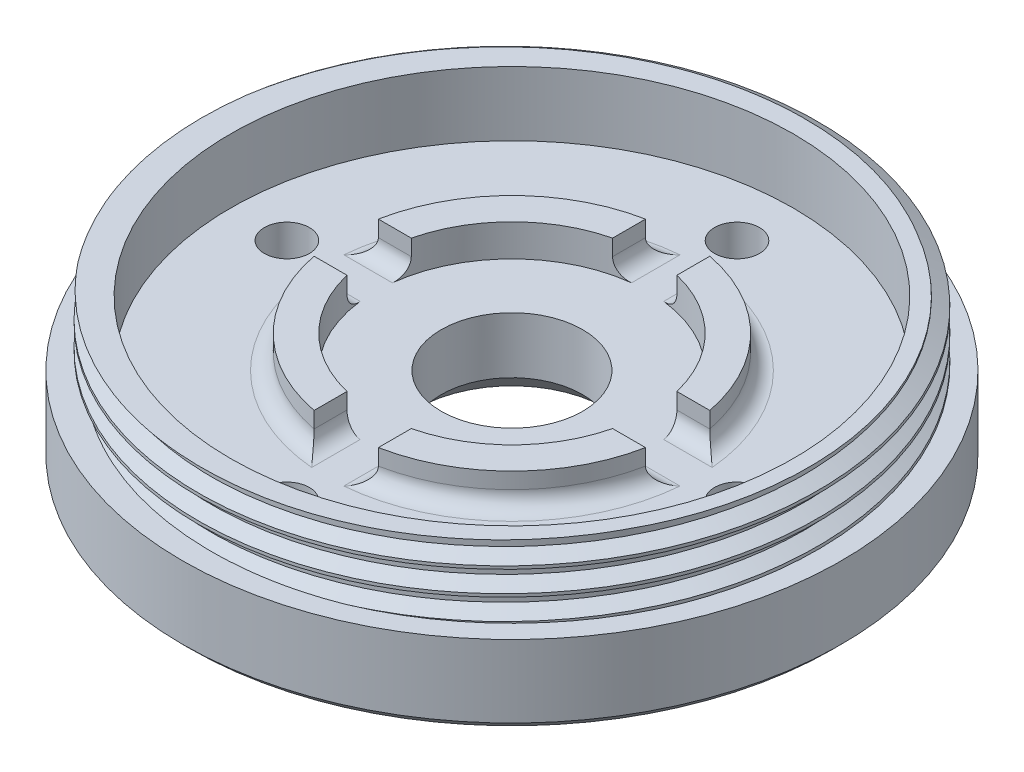
SolidWorks part; units mm, degrees
ref_plane "Front plane" through (0, 0, 0) normal (0, 0, 1) x (1, 0, 0)
ref_plane "Top plane" through (0, 0, 0) normal (0, 1, 0) x (1, 0, 0)
ref_plane "Right plane" through (0, 0, 0) normal (1, 0, 0) x (0, 0, -1)
ref_axis "Axis X" through (0, 0, 0) along (1, 0, 0)
ref_axis "Axis Y" through (0, 0, 0) along (0, 1, 0)
ref_axis "Axis Z" through (0, 0, 0) along (0, 0, 1)
sketch "Sketch1" plane through (0, 0, 0) normal (0, 1, 0) x (1, 0, 0)
  circle A0 centre (0, 0) radius 20.5
  circle A1 centre (0, 0) radius 4.4
  circle A2 centre (0, 0) radius 14 construction
  circle A3 centre (0, 14) radius 1.4
  circle A4 centre (14, 0) radius 1.4
  circle A5 centre (0, -14) radius 1.4
  circle A6 centre (-14, 0) radius 1.4
  point P16 (0, 0)
  dimension "D1" = 41
  dimension "D2" = 8.8
  dimension "D3" = 28
  dimension "D4" = 2.8
  dimension "D5" = 4
extrude "Extrude1" add sketch "Sketch1" along normal blind 5
sketch "Sketch8" plane through (0, 5, 0) normal (0, 1, 0) x (1, 0, 0)
  circle A1 centre (0, 0) radius 17.5
  circle A3 centre (0, 0) radius 18.45
  dimension "D1" = 35
  dimension "D2" = 0.95
extrude "Бобышка-Вытянуть1" add sketch "Sketch8" along normal blind 4
thread "Резьба1" pitch 1.5 method extrude trim with start face yes trim with end face yes profile "Профиль резьбы1" start angle 0, offset 2, length 0, pitch 1.5, diameter 36.9
ref_plane "Плоскость1" through (-18.45, 11, 0) normal (0, 0, 1) x (-1, 0, 0)
sketch "Профиль резьбы1" plane through (-18.45, 11, 0) normal (0, 0, 1) x (-1, 0, 0)
  line L0 (0, 0) -> (0, 1.5) construction
  line L1 (0, 0) -> (0.8119, 0.4687)
  line L2 (0.8119, 0.4687) -> (0.8119, 0.6562)
  line L3 (0.8119, 0.6562) -> (0, 1.125)
  line L4 (0.8119, 0.5625) -> (0, 0.5625) construction
  line L11 (0, 0) -> (0, 1.125)
  point P2 (0, 0)
  dimension "Pitch" = 1.5
  dimension "Profile_Angle" = 60
  dimension "Profile_Land" = 0.1875
  dimension "Profile_Height" = 0.8119
sketch "Эскиз3" plane through (0, 5, 0) normal (0, 1, 0) x (1, 0, 0)
  line L0 (0, 0) -> (0, 10) construction
  line L1 (-2, 10.3078) -> (-2, 8.2614)
  line L2 (2, 10.3078) -> (2, 8.2614)
  line L3 (10.3078, 2) -> (8.2614, 2)
  line L4 (10.3078, -2) -> (8.2614, -2)
  line L5 (2, -10.3078) -> (2, -8.2614)
  line L6 (-2, -10.3078) -> (-2, -8.2614)
  line L7 (-10.3078, -2) -> (-8.2614, -2)
  line L8 (-10.3078, 2) -> (-8.2614, 2)
  arc A0 (-2, 8.2614) -> (-8.2614, 2) centre (0, 0) ccw
  arc A1 (-2, 10.3078) -> (-10.3078, 2) centre (0, 0) ccw
  arc A2 (8.2614, 2) -> (2, 8.2614) centre (0, 0) ccw
  arc A3 (10.3078, 2) -> (2, 10.3078) centre (0, 0) ccw
  arc A4 (-8.2614, -2) -> (-2, -8.2614) centre (0, 0) ccw
  arc A5 (-10.3078, -2) -> (-2, -10.3078) centre (0, 0) ccw
  arc A6 (2, -8.2614) -> (8.2614, -2) centre (0, 0) ccw
  arc A7 (2, -10.3078) -> (10.3078, -2) centre (0, 0) ccw
  dimension "D1" = 17
  dimension "D2" = 2
  dimension "D3" = 4
  dimension "D4" = 4
extrude "Бобышка-Вытянуть2" add sketch "Эскиз3" along normal blind 2
fillet "Скругление1" radius 1 12 edges at (-2, 5, -9.2846) (2, 5, -9.2846) (7.4246, 5, -7.4246) (9.2846, 5, -2) (9.2846, 5, 2) (7.4246, 5, 7.4246) (-7.4246, 5, -7.4246) (-7.4246, 5, 7.4246) (2, 5, 9.2846) (-2, 5, 9.2846) (-9.2846, 5, 2) (-9.2846, 5, -2)
chamfer "Chamfer2" distance 1.5 angle 45 1 edges at (0, 0, 4.4)
chamfer "Chamfer3" distance 0.5 angle 45 1 edges at (0, 0, 20.5)
chamfer "Chamfer4" distance 1 angle 45 4 edges at (0, 0, -12.6) (14, 0, 1.4) (-14, 0, 1.4) (0, 0, 15.4)
equation "\"motor_D\"= 30'Motor diameter"
equation "\"motor_H\"= 13'Motor heigh"
equation "\"motor_d1\"= 25.4558'Seating diameter of screws on the fixed part of the motor"
equation "\"motor_s1\"= 2'Screws diameter on the fixed part of motor"
equation "\"motor_a2\"= 10'Seating parameter in rectangle of screws on the moving part of the motor"
equation "\"motor_s2\"= 2'Screws diameter on the moving part of motor"
equation "\"motor_Dc\"= 5'Central hole diameter of motor"
equation "\"bearing_d1\"= 6'Bearing inner diameter"
equation "\"bearing_d2\"= 17'Bearing external diameter"
equation "\"bearing h\"= 6'Bearing heigh"
equation "\"pin_d\"= 2'Pin diameter"
equation "\"pin_h\"= 12'Pin heigh"
equation "\"magnet_d1\"= 5'Magnet inner diameter"
equation "\"magnet_d2\"= 9.5'Magnet external diameter"
equation "\"magnet_h\"= 3'Magnet heigh"
equation "\"motor_b2\"= 22'Seating parameter in rectangle of screws on the moving part of the motor"
equation "\"motor_d2\"= 0'Seating diameter of screws on the moving part of the motor (if this parameter is not determine, write 0)"
equation "\"motor_cmd\"= 12'Central magnet mount diameter"
equation "\"motor_cmh\"= 1.4'Central magnet mount heigh (if not write 0)"
equation "\"motor_whR\"= 10'Distance from center of motor to wires"
equation "\"D1@Sketch1\"= IIF ( \"motor_D\" < 34 , 41 , \"motor_D\" + 8 )"
equation "\"D2@Sketch1\"=\"ft_sensor_d1\"-1"
equation "\"D4@Sketch1\"=3-\"print_offset\""
equation "\"print_offset\"= 0.2'Offset for printing holes"
equation "\"ft_sensor_d1\"= 9.8"
equation "\"ft_sensor_d2\"= 24.9"
equation "\"ft_sensor_d3\"= 22.6'Inner diameter of "
equation "\"ft_sensor_h\"= 7.1"
equation "\"ft_sensor_whD\"= 5"
equation "\"D1@Sketch8\" = IIF ( \"motor_D\" < 34 , 41 , \"motor_D\" + 8 ) - 6"
equation "\"D2@Sketch8\"= 0.95"
equation "\"D1@Эскиз3\"=\"bearing_d2\""
equation "\"D1@Бобышка-Вытянуть2\"=\"bearing h\"/3"
